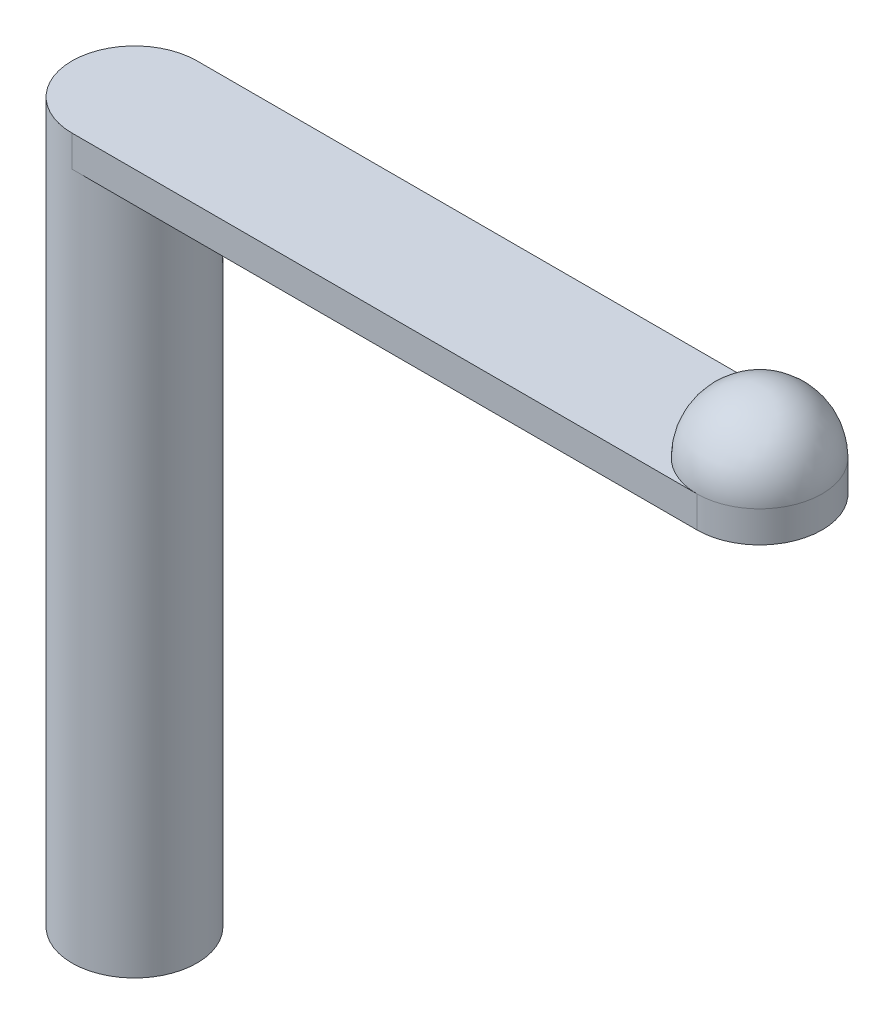
SolidWorks part; units mm, degrees
ref_plane "Front Plane" through (0, 0, 0) normal (0, 0, 1) x (1, 0, 0)
ref_plane "Top Plane" through (0, 0, 0) normal (0, 1, 0) x (1, 0, 0)
ref_plane "Right Plane" through (0, 0, 0) normal (1, 0, 0) x (0, 0, -1)
sketch "Sketch2" plane through (0, 0, 0) normal (0, 1, 0) x (1, 0, 0)
  circle A0 centre (0, 0) radius 10
extrude "Boss-Extrude1" add sketch "Sketch2" along normal blind 110
sketch "Sketch3" plane through (0, 110, 0) normal (0, 1, 0) x (1, 0, 0)
  line L0 (0, 10) -> (100, 10)
  line L1 (0, -10) -> (100, -10)
  arc A0 (0, 10) -> (0, -10) centre (0, 0) ccw
  circle A1 centre (0, 0) radius 10 construction
  arc A2 (100, 10) -> (100, -10) centre (100, 0) cw
extrude "Boss-Extrude2" add sketch "Sketch3" along normal blind 5
sketch "Sketch4" plane through (0, 115, 0) normal (0, 1, 0) x (1, 0, 0)
  circle A0 centre (100, 0) radius 10
extrude "Boss-Extrude3" add sketch "Sketch4" along normal blind 0.001
sketch "Sketch5" plane through (0, 115.001, 0) normal (0, 1, 0) x (1, 0, 0)
  circle A0 centre (100, 0) radius 10
extrude "Boss-Extrude4" add sketch "Sketch5" along normal blind 10
fillet "Fillet1" radius 10 1 edges at (100, 125.001, 10)
